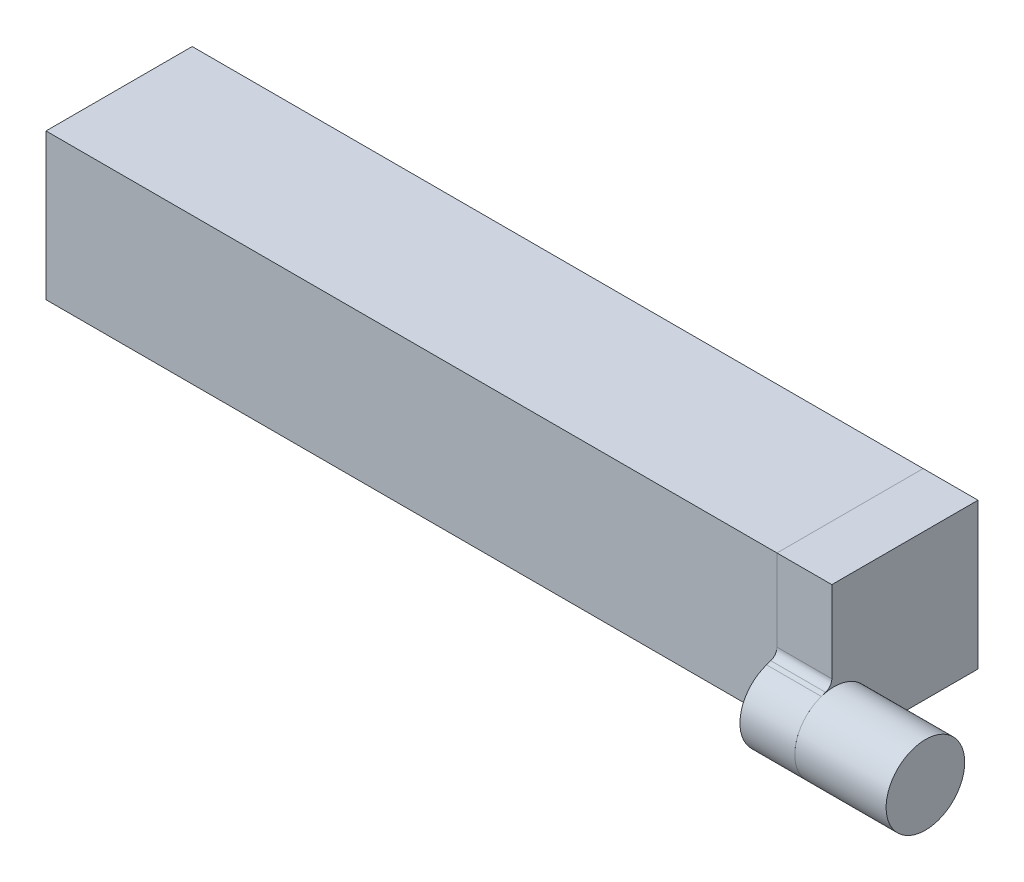
SolidWorks part; units mm, degrees
ref_plane "Front Plane" through (0, 0, 0) normal (0, 0, 1) x (1, 0, 0)
ref_plane "Top Plane" through (0, 0, 0) normal (0, 1, 0) x (1, 0, 0)
ref_plane "Right Plane" through (0, 0, 0) normal (1, 0, 0) x (0, 0, -1)
sketch "Sketch2" plane through (0, 0, 0) normal (1, 0, 0) x (0, 0, -1)
  line L1 (-2.4, -2.4) -> (2.4, -2.4)
  line L2 (-2.4, -2.4) -> (-2.4, 2.4)
  line L3 (-2.4, 2.4) -> (2.4, 2.4)
  line L4 (2.4, -2.4) -> (2.4, 2.4)
  line L5 (-2.4, -2.4) -> (2.4, 2.4) construction
  line L6 (-2.4, 2.4) -> (2.4, -2.4) construction
  line L7 (4, -4) -> (-4, -4)
  line L8 (4, -4) -> (4, 4)
  line L9 (4, 4) -> (-4, 4)
  line L10 (-4, -4) -> (-4, 4)
  line L11 (4, -4) -> (-4, 4) construction
  line L12 (4, 4) -> (-4, -4) construction
  point P0 (0, 0)
  point P5 (0, 0)
  dimension "D1" = 4.8
  dimension "D2" = 4.8
  dimension "D3" = 8
  dimension "D4" = 8
  dimension "D5" = 1.6
extrude "Boss-Extrude1" add sketch "Sketch2" along normal blind 10
extrude "Boss-Extrude2" add sketch "Sketch2<2>" along normal blind 25 from offset 15 contours L1 L4 L3 L2 | L10 L7 L8 L9 L4 L1 L2 L3 region at (0, 0, 0) region at (0, -3.8869, 0)
sketch "Sketch2<2>" plane through (0, 0, 0) normal (1, 0, 0) x (0, 0, -1) same geometry as "Sketch2"
sketch "Sketch5" plane through (40, 0, 0) normal (1, 0, 0) x (0, 0, -1)
  line L6 (-4, 4) -> (4, 4)
  line L7 (4, 4) -> (4, -4)
  line L8 (4, -4) -> (0, -4)
  line L9 (-4, -4) -> (4, -4) construction
  line L10 (0, -4) -> (-3.1836, -5.0857)
  line L11 (-4.5715, -1.0158) -> (-4, -0.8209)
  line L12 (-4, -4) -> (-4, 4) construction
  line L13 (-4.5715, -1.0158) -> (-3.1836, -5.0857) construction
  line L14 (-4, -0.8209) -> (-4, 4)
  arc A1 (-4.5715, -1.0158) -> (-3.1836, -5.0857) centre (-3.8775, -3.0507) ccw
  dimension "D3" = 8
  dimension "D4" = 4.3
extrude "Boss-Extrude3" add sketch "Sketch5" along normal blind 3
sketch "Sketch6" plane through (43, 0, 0) normal (1, 0, 0) x (0, 0, -1)
  circle A1 centre (-3.8775, -3.0507) radius 2.15
  dimension "D1" = 4.3
extrude "Boss-Extrude4" add sketch "Sketch6" along normal blind 5
extrude "Boss-Extrude5" add sketch "Sketch2<4>" along normal blind 5 from offset 10
sketch "Sketch2<4>" plane through (0, 0, 0) normal (1, 0, 0) x (0, 0, -1) same geometry as "Sketch2"
fillet "Fillet1" radius 0.5 4 edges at (0, -2.4, 0) (0, 0, -2.4) (0, 0, 2.4) (0, 2.4, 0)
fillet "Fillet2" radius 0.5 1 edges at (41.5, -0.8209, 4)
